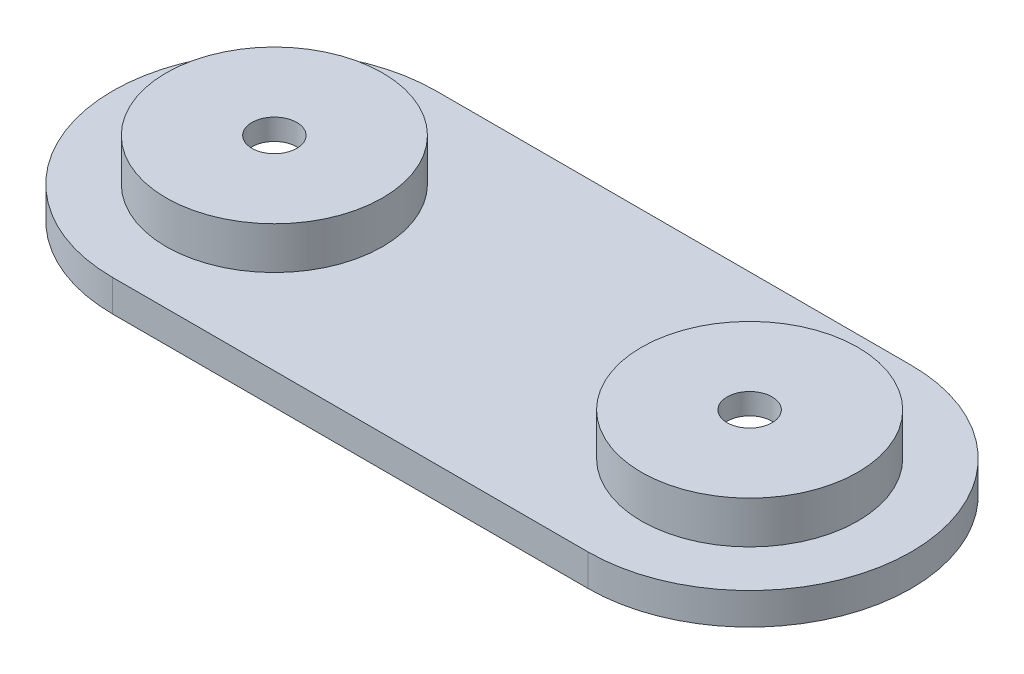
SolidWorks part; units mm, degrees
ref_plane "Front Plane" through (0, 0, 0) normal (0, 0, 1) x (1, 0, 0)
ref_plane "Top Plane" through (0, 0, 0) normal (0, 1, 0) x (1, 0, 0)
ref_plane "Right Plane" through (0, 0, 0) normal (1, 0, 0) x (0, 0, -1)
sketch "Sketch1" plane through (0, 0, 0) normal (0, 1, 0) x (1, 0, 0)
  line L0 (22.5, 0) -> (-22.5, 0)
  line L1 (-22.5, -30.6106) -> (22.5, -30.6106)
  arc A0 (-22.5, 0) -> (-22.5, -30.6106) centre (-22.5, -15.3053) ccw
  arc A1 (22.5, -30.6106) -> (22.5, 0) centre (22.5, -15.3053) ccw
  point P4 (0, 0)
  dimension "D1" = 45
  dimension "D2" = 30.6106
extrude "Boss-Extrude1" add sketch "Sketch1" along normal blind 3
sketch "Sketch2" plane through (0, 3, 0) normal (0, 1, 0) x (1, 0, 0)
  line L0 (-22.5, 0) -> (-22.5, -30.6106) construction
  line L1 (0, 0) -> (0, -30.6106) construction
  line L2 (-22.5, -30.6106) -> (22.5, -30.6106) construction
  circle A0 centre (-22.5, -15.3053) radius 9.5
  circle A2 centre (22.5, -15.3053) radius 9.5
  dimension "D1" = 19
extrude "Cut-Extrude1" cut sketch "Sketch2" against normal through all
sketch "Sketch3" plane through (0, 3, 0) normal (0, 1, 0) x (1, 0, 0)
  circle A0 centre (22.5, -15.3053) radius 9.5 construction
  circle A1 centre (22.5, -15.3053) radius 9.5
  circle A2 centre (-22.5, -15.3053) radius 9.5 construction
  circle A3 centre (-22.5, -15.3053) radius 9.5
  circle A4 centre (22.5, -15.3053) radius 10.25
  circle A5 centre (-22.5, -15.3053) radius 10.25
  dimension "D1" = 20.5
extrude "Boss-Extrude2" add sketch "Sketch3" along normal blind 2
sketch "Sketch4" plane through (0, 5, 0) normal (0, 1, 0) x (1, 0, 0)
  circle A0 centre (22.5, -15.3053) radius 10.25 construction
  circle A1 centre (22.5, -15.3053) radius 10.25
  circle A2 centre (-22.5, -15.3053) radius 10.25 construction
  circle A3 centre (-22.5, -15.3053) radius 10.25
extrude "Boss-Extrude3" add sketch "Sketch4" along normal blind 2
sketch "Sketch5" plane through (0, 7, 0) normal (0, 1, 0) x (1, 0, 0)
  circle A0 centre (22.5, -15.3053) radius 2.125
  circle A1 centre (-22.5, -15.3053) radius 2.125
  dimension "D1" = 4.25
extrude "Cut-Extrude2" cut sketch "Sketch5" against normal blind 2
